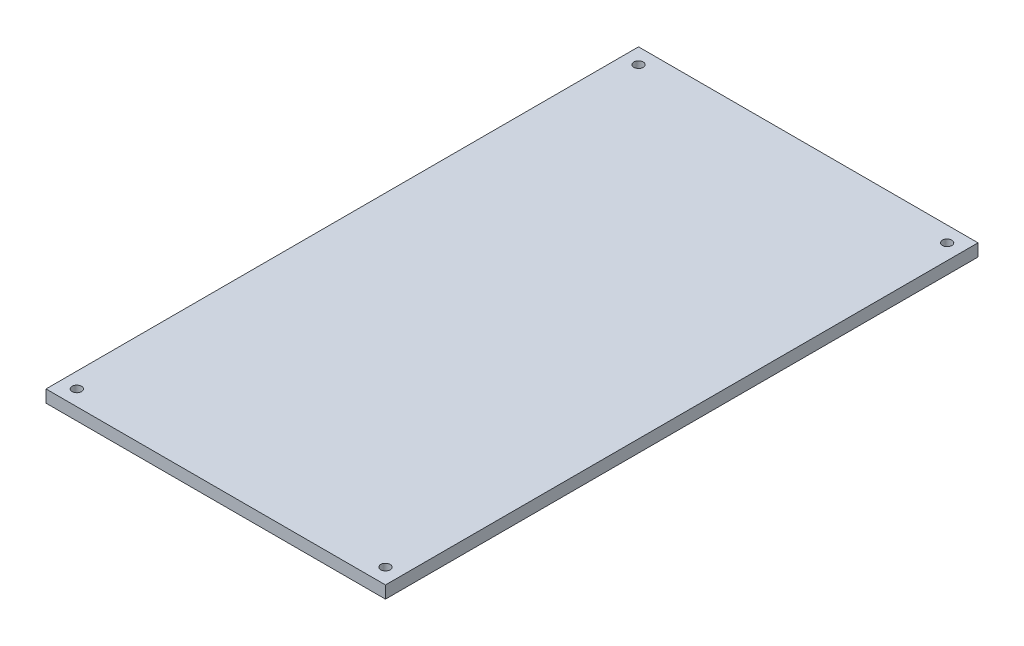
SolidWorks part; units mm, degrees
material "PCB (FR-4) (Recolor)"
ref_plane "Front Plane" through (0, 0, 0) normal (0, 0, 1) x (1, 0, 0)
ref_plane "Top Plane" through (0, 0, 0) normal (0, 1, 0) x (1, 0, 0)
ref_plane "Right Plane" through (0, 0, 0) normal (1, 0, 0) x (0, 0, -1)
sketch "Sketch2" plane through (0, 0, 0) normal (0, 1, 0) x (1, 0, 0)
  line L1 (0, 0) -> (55, 0)
  line L2 (0, 0) -> (0, 96)
  line L3 (0, 96) -> (55, 96)
  line L4 (55, 0) -> (55, 96)
  dimension "D1" = 96
  dimension "D2" = 55
extrude "Boss-Extrude1" add sketch "Sketch2" along normal blind 2
sketch "Sketch3" plane through (0, 2, 0) normal (0, 1, 0) x (1, 0, 0)
  line L0 (2.5, 2.5) -> (52.5, 2.5) construction
  line L1 (52.5, 2.5) -> (52.5, 93.5) construction
  line L2 (0, 0) -> (55, 0) construction
  line L3 (55, 0) -> (55, 96) construction
  line L4 (0, 96) -> (0, 0) construction
  line L5 (55, 96) -> (0, 96) construction
  line L6 (2.5, 93.5) -> (52.5, 93.5) construction
  line L9 (2.5, 93.5) -> (2.5, 2.5) construction
  circle A0 centre (2.5, 2.5) radius 0.762
  circle A1 centre (52.5, 2.5) radius 0.762
  circle A2 centre (52.5, 93.5) radius 0.762
  circle A3 centre (2.5, 93.5) radius 0.762
  dimension "D1" = 1.524
  dimension "D2" = 2.5
  dimension "D3" = 2.5
  dimension "D4" = 2.5
  dimension "D5" = 2.5
extrude "Cut-Extrude1" cut sketch "Sketch3" against normal through all
